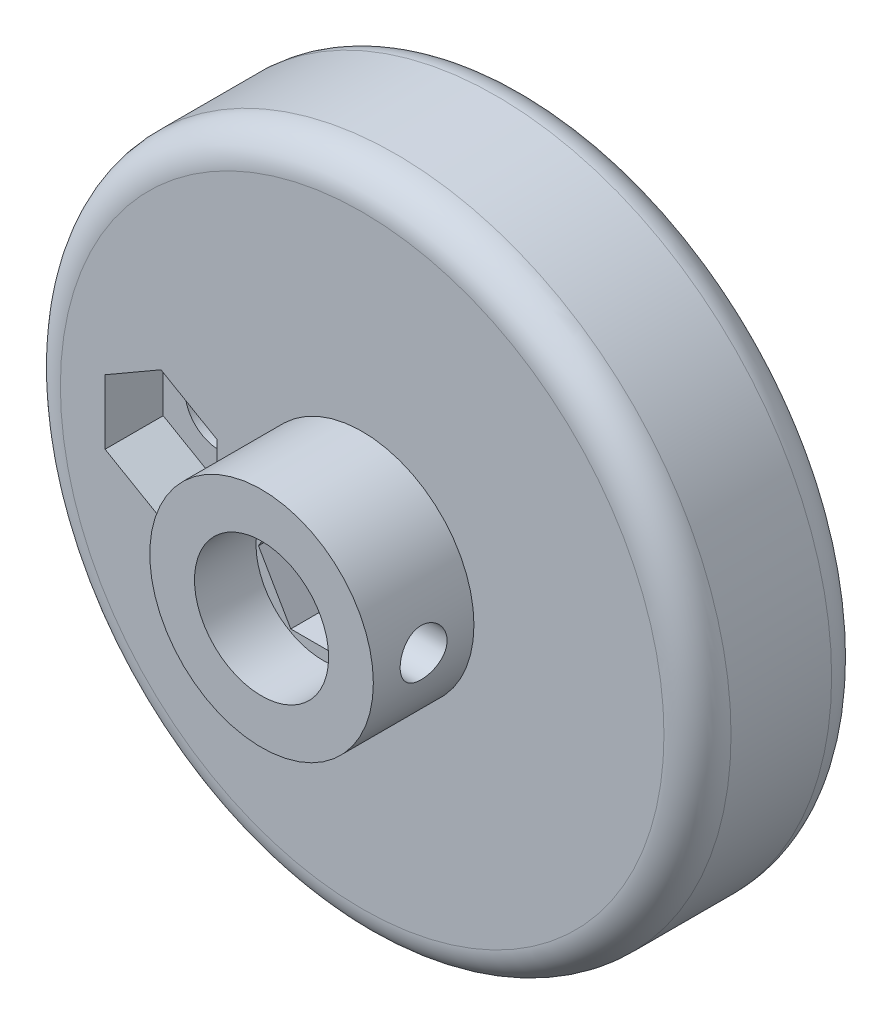
SolidWorks part; units mm, degrees
ref_plane "Front Plane" through (0, 0, 0) normal (0, 0, 1) x (1, 0, 0)
ref_plane "Top Plane" through (0, 0, 0) normal (0, 1, 0) x (1, 0, 0)
ref_plane "Right Plane" through (0, 0, 0) normal (1, 0, 0) x (0, 0, -1)
sketch "Sketch1" plane through (0, 0, 0) normal (0, 0, 1) x (1, 0, 0)
  circle A0 centre (0, 0) radius 30
  dimension "D1" = 60
extrude "Boss-Extrude1" add sketch "Sketch1" along normal blind 15
sketch "Sketch2" plane through (0, 0, 15) normal (0, 0, 1) x (1, 0, 0)
  circle A0 centre (0, 0) radius 10
  dimension "D1" = 20
extrude "Boss-Extrude2" add sketch "Sketch2" along normal blind 9
sketch "Sketch3" plane through (0, 0, 24) normal (0, 0, 1) x (1, 0, 0)
  circle A0 centre (0, 0) radius 3.175
  dimension "D1" = 6.35
extrude "Cut-Extrude1" cut sketch "Sketch3" against normal through all
fillet "Fillet1" radius 3 2 edges at (30, 0, 0) (30, 0, 15)
sketch "Sketch4" plane through (0, 0, 0) normal (0, 0, -1) x (-1, 0, 0)
  circle A0 centre (0, 0) radius 6
  dimension "D1" = 12
extrude "Cut-Extrude2" cut sketch "Sketch4" against normal blind 4
fillet "Fillet2" radius 1 1 edges at (-6, 0, 0)
hole_wizard "M5x0.8 Tapped Hole1" positions "Sketch6" profile "Sketch5" tap size "M5x0.8" standard "ANSI Metric" end condition through all
sketch "Sketch6" plane through (0, 0, 0) normal (1, 0, 0) x (0, 0, -1)
  line L0 (-15, 10) -> (-15, -10) construction
  line L1 (-1000, 0) -> (49000, 0) construction
  point P0 (-19.5, 0)
  dimension "D1" = 4.5
sketch "Sketch5" plane through (0, 0, 19.5) normal (0, 1, 0) x (0, 0, 1)
  line L0 (0, 0) -> (0, 30)
  line L1 (0, 30) -> (2.1, 30)
  line L2 (2.1, 30) -> (2.1, 0)
  line L5 (2.1, 0) -> (0, 0)
  line L11 (0, -6.35) -> (0, 107.95) construction
  dimension "Thru Tap Drill Dia." = 4.2
  dimension "Thru Tap Drill Depth" = 30
cosmetic thread "Hole Thread1" parameters "D2"=5
sketch "Sketch8" plane through (0, 0, 15) normal (0, 0, 1) x (1, 0, 0)
  line L0 (-1000, 0) -> (49000, 0) construction
  circle A0 centre (-18, 0) radius 3.05
  dimension "D1" = 6.1
  dimension "D2" = 18
extrude "Cut-Extrude3" cut sketch "Sketch8" against normal through all
sketch "Sketch7" plane through (0, 0, 15) normal (0, 0, 1) x (1, 0, 0)
  line L1 (-23, 2.8868) -> (-23, -2.8868)
  line L2 (-23, -2.8868) -> (-18, -5.7735)
  line L3 (-18, -5.7735) -> (-13, -2.8868)
  line L4 (-13, -2.8868) -> (-13, 2.8868)
  line L5 (-13, 2.8868) -> (-18, 5.7735)
  line L6 (-18, 5.7735) -> (-23, 2.8868)
  circle A0 centre (-18, 0) radius 5 construction
  circle A1 centre (-18, 0) radius 3.05 construction
  dimension "D1" = 10
extrude "Cut-Extrude4" cut sketch "Sketch7" against normal blind 5.2
sketch "Sketch9" plane through (0, 0, 24) normal (0, 0, 1) x (1, 0, 0)
  circle A0 centre (0, 0) radius 6
  dimension "D1" = 12
extrude "Cut-Extrude5" cut sketch "Sketch9" against normal blind 5.5
sketch "Sketch10" plane through (0, 0, 18.5) normal (0, 0, 1) x (1, 0, 0)
  line L1 (5.7735, 0) -> (2.8868, 5)
  line L2 (2.8868, 5) -> (-2.8868, 5)
  line L3 (-2.8868, 5) -> (-5.7735, 0)
  line L4 (-5.7735, 0) -> (-2.8868, -5)
  line L5 (-2.8868, -5) -> (2.8868, -5)
  line L6 (2.8868, -5) -> (5.7735, 0)
  circle A0 centre (0, 0) radius 5 construction
  dimension "D1" = 10
extrude "Cut-Extrude6" cut sketch "Sketch10" against normal blind 5.5
